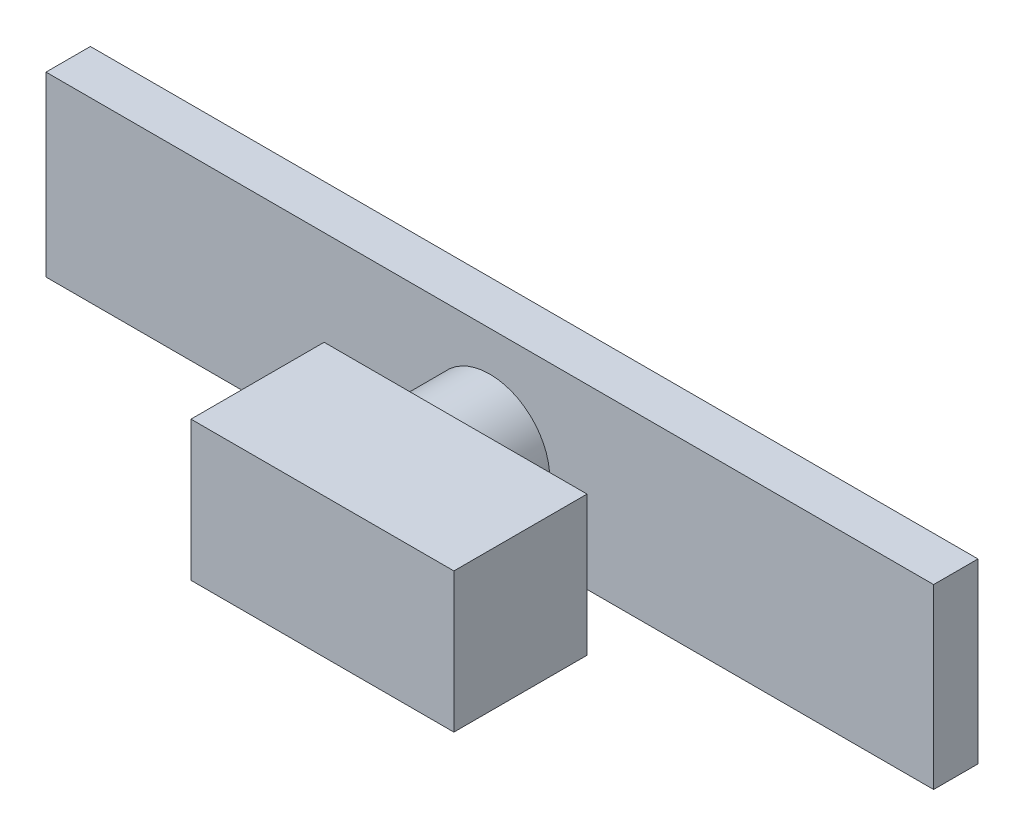
SolidWorks part; units mm, degrees
ref_plane "Front Plane" through (0, 0, 0) normal (0, 0, 1) x (1, 0, 0)
ref_plane "Top Plane" through (0, 0, 0) normal (0, 1, 0) x (1, 0, 0)
ref_plane "Right Plane" through (0, 0, 0) normal (1, 0, 0) x (0, 0, -1)
sketch "Sketch2" plane through (0, 0, 0) normal (0, 0, 1) x (1, 0, 0)
  line L1 (-47.8692, 21.2481) -> (206.1308, 21.2481)
  line L2 (-47.8692, 21.2481) -> (-47.8692, 8.5481)
  line L3 (-47.8692, 8.5481) -> (206.1308, 8.5481)
  line L4 (206.1308, 21.2481) -> (206.1308, 8.5481)
  dimension "D1" = 12.7
  dimension "D2" = 254
extrude "Boss-Extrude1" add sketch "Sketch2" along normal blind 50.8
sketch "Sketch3" plane through (0, 21.2481, 0) normal (0, 1, 0) x (1, 0, 0)
  circle A0 centre (79.1308, -28.4831) radius 17.1408
extrude "Boss-Extrude2" add sketch "Sketch3" along normal blind 19.05
sketch "Sketch4" plane through (0, 40.2981, 0) normal (0, 1, 0) x (1, 0, 0)
  line L1 (50.7675, -8.111) -> (126.0034, -8.111)
  line L2 (50.7675, -8.111) -> (50.7675, -48.0661)
  line L3 (50.7675, -48.0661) -> (126.0034, -48.0661)
  line L4 (126.0034, -8.111) -> (126.0034, -48.0661)
extrude "Boss-Extrude3" add sketch "Sketch4" along normal blind 38.1
scale "Scale2" scale about centroid uniform scaling yes scale factor 0.06
move or copy body "Body-Move/Copy1" bodies to move or copy 105 copy no rotation origin (0, 33.6669, 26.5501) rotation axis (1, 0, 0) rotation angle 90
move or copy body "Body-Move/Copy3" bodies to move or copy 106 copy no translate (-50.8, 0, -50.8)
scale "Scale5" scale about centroid uniform scaling yes scale factor 0.25
move or copy body "Body-Move/Copy9" bodies to move or copy 111 copy no translate (-50.8, 0, 0)
move or copy body "Body-Move/Copy13" bodies to move or copy 117 copy no translate (0, -50.8, 0)
